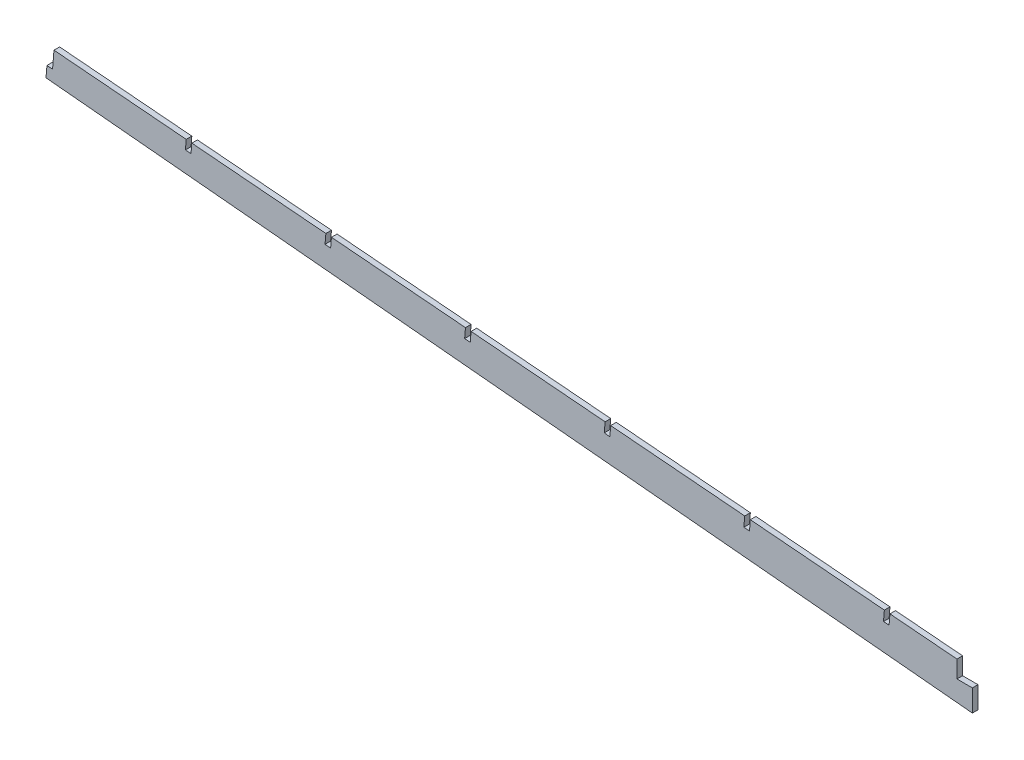
SolidWorks part; units mm, degrees
ref_plane "Front Plane" through (0, 0, 0) normal (0, 0, 1) x (1, 0, 0)
ref_plane "Top Plane" through (0, 0, 0) normal (0, 1, 0) x (1, 0, 0)
ref_plane "Right Plane" through (0, 0, 0) normal (1, 0, 0) x (0, 0, -1)
sketch "Sketch1" plane through (0, 0, 0) normal (0, 0, 1) x (1, 0, 0)
  line L0 (-951.0618, 63.2916) -> (-11.5367, -24.9026)
  line L8 (-8.3728, -25.1683) -> (-6.7788, -6.1851) construction
  line L9 (-6.7788, -6.1851) -> (-9.9426, -5.9194)
  line L10 (-9.9426, -5.9194) -> (-11.5367, -24.9026) construction
  line L11 (-11.5367, -24.9026) -> (-8.3728, -25.1683)
  line L12 (3.175, -25.5459) -> (3.175, -6.4959) construction
  line L13 (3.175, -6.4959) -> (0, -6.4959)
  line L14 (0, -6.4959) -> (0, -25.5459) construction
  line L15 (0, -25.5459) -> (3.175, -25.5459)
  line L17 (-943.9754, 109.7383) -> (-947.3666, 69.3536)
  line L19 (-8.3728, -25.1683) -> (0, -25.5459)
  line L20 (3.175, -25.5459) -> (152.4, -25.5459)
  line L21 (25.4, -0.1459) -> (69.85, -7.7659)
  line L22 (25.4, -0.1459) -> (-2.8123, -0.1459)
  line L23 (-2.8123, -0.1459) -> (-946.5481, 79.1019)
  line L24 (0, -6.4959) -> (0, -0.1459)
  line L25 (3.175, -6.4959) -> (3.175, -0.1459)
  line L26 (-6.7788, -6.1851) -> (-6.2474, 0.1426)
  line L27 (-9.9426, -5.9194) -> (-9.4113, 0.4083)
  line L28 (-9.9426, -5.9194) -> (-946.998, 73.7432)
  line L29 (69.85, -7.7659) -> (152.4, -7.7659)
  line L30 (152.4, -7.7659) -> (152.4, -25.5459)
  line L31 (76.2, -7.7659) -> (76.2, -25.5459)
  line L32 (79.375, -7.7659) -> (79.375, -25.5459)
  line L33 (76.2, -12.8459) -> (79.375, -12.8459)
  line L34 (15.875, -0.1459) -> (15.875, -5.2259)
  line L35 (15.875, -5.2259) -> (19.05, -5.2259)
  line L36 (19.05, -5.2259) -> (19.05, -0.1459)
  line L37 (92.075, -7.7659) -> (92.075, -12.8459)
  line L38 (92.075, -12.8459) -> (95.25, -12.8459)
  line L39 (95.25, -12.8459) -> (95.25, -7.7659)
  line L40 (136.525, -7.7659) -> (136.525, -12.8459)
  line L41 (136.525, -12.8459) -> (139.7, -12.8459)
  line L42 (139.7, -12.8459) -> (139.7, -7.7659)
  line L44 (-951.0618, 63.2916) -> (-950.5305, 69.6193)
  line L45 (-950.5305, 69.6193) -> (-947.3666, 69.3536)
  dimension "D1" = 25.4
  dimension "D2" = 6.35
extrude "Boss-Extrude1" add sketch "Sketch1" along normal blind 3.175 contours L31 L29 L21 L22 L25 L13 L24 L23 L26 L9 L28 L17 L11 L19 L15 L20 | L33 L31 L20 L32 | L29 L32 L20 L30 | L28 L27 L23 L17 | L45 L44 L17 region at (-380.2142, 18.2171, 0) region at (-465.2737, 35.7392, 0) region at (77.7875, -19.1959, 0) region at (115.8875, -16.8176, 0)
sketch "Sketch2" plane through (0, 0, 3.175) normal (0, 0, 1) x (1, 0, 0)
  line L1 (-73.9963, 64.5177) -> (-80.9723, -18.558)
  line L3 (-77.1601, 64.7834) -> (-84.1362, -18.2923)
  line L5 (-153.17, 68.7234) -> (-159.8855, -11.2491)
  line L7 (-232.3428, 72.9404) -> (-238.7996, -3.951)
  line L9 (-311.5203, 77.1018) -> (-317.7101, 3.3887)
  line L11 (-390.6978, 81.2631) -> (-396.6209, 10.7264)
  line L13 (-469.8812, 85.3537) -> (-475.5272, 18.1169)
  line L15 (-549.0652, 89.4374) -> (-554.4332, 25.5108)
  line L17 (-628.256, 93.4393) -> (-633.334, 32.9679)
  line L19 (-707.4489, 97.4177) -> (-712.2332, 40.4425)
  line L21 (-786.6506, 101.2897) -> (-791.1254, 48.0007)
  line L23 (-865.8569, 105.1088) -> (-870.014, 55.603)
  line L25 (-235.5067, 73.2061) -> (-241.9634, -3.6853)
  line L27 (-314.6841, 77.3675) -> (-320.874, 3.6544)
  line L29 (-393.8616, 81.5287) -> (-399.7848, 10.992)
  line L31 (-473.045, 85.6194) -> (-478.6911, 18.3826)
  line L33 (-552.229, 89.7031) -> (-557.5971, 25.7765)
  line L35 (-631.4199, 93.705) -> (-636.4978, 33.2336)
  line L37 (-710.6127, 97.6833) -> (-715.3971, 40.7082)
  line L39 (-789.8145, 101.5554) -> (-794.2893, 48.2664)
  line L41 (-9.9426, -5.9194) -> (-946.998, 73.7432)
  line L43 (-9.4113, 0.4083) -> (-946.5481, 79.1019)
  line L45 (-156.3339, 68.9891) -> (-163.0494, -10.9834)
  line L47 (-869.0207, 105.3745) -> (-873.1778, 55.8686)
  line M13 (-9.4113, 0.4083) -> (-946.5481, 79.1019)
extrude "Cut-Extrude1" cut sketch "Sketch2" against normal through all contours L47 L41 L23 M13 | L41 L21 L39 M13 | L41 L19 L37 M13 | L41 L17 L35 M13 | L41 L15 L33 M13 | L41 L13 L31 M13 | L41 L11 L29 M13 | L41 L9 L27 M13 | L41 L7 L25 M13 | L45 L41 L5 M13 | L41 L1 L3 M13 region at (-80.7341, 3.2483, 3.175) region at (-159.7008, 9.9204, 3.175) region at (-238.6674, 16.5925, 3.175) region at (-317.6341, 23.2647, 3.175) region at (-396.6007, 29.9368, 3.175) region at (-475.5673, 36.6089, 3.175) region at (-554.534, 43.281, 3.175) region at (-633.5006, 49.9532, 3.175) region at (-712.4672, 56.6253, 3.175) region at (-791.4339, 63.2974, 3.175) region at (-870.4005, 69.9696, 3.175)
sketch "Sketch3" plane through (0, 0, 3.175) normal (0, 0, 1) x (1, 0, 0)
  line L0 (-435.837, 36.2162) -> (-435.837, 26.4516)
  line L1 (-397.9339, 33.0334) -> (-473.7401, 39.3991) construction
  line L2 (-435.837, 26.4516) -> (-427.1156, 26.4516)
  line L3 (-427.1156, 26.4516) -> (-427.1156, 14.1082)
  line L4 (-951.0618, 63.2916) -> (-11.5367, -24.9026) construction
  line L5 (-435.837, 36.2162) -> (191.1966, 26.4516)
  line L6 (191.1966, 26.4516) -> (150.839, -84.0542)
  line L7 (150.839, -84.0542) -> (-427.1156, 14.1082)
extrude "Cut-Extrude2" cut sketch "Sketch3" against normal blind 7.62 contours L7 L3 L2 L0 L5 L6
